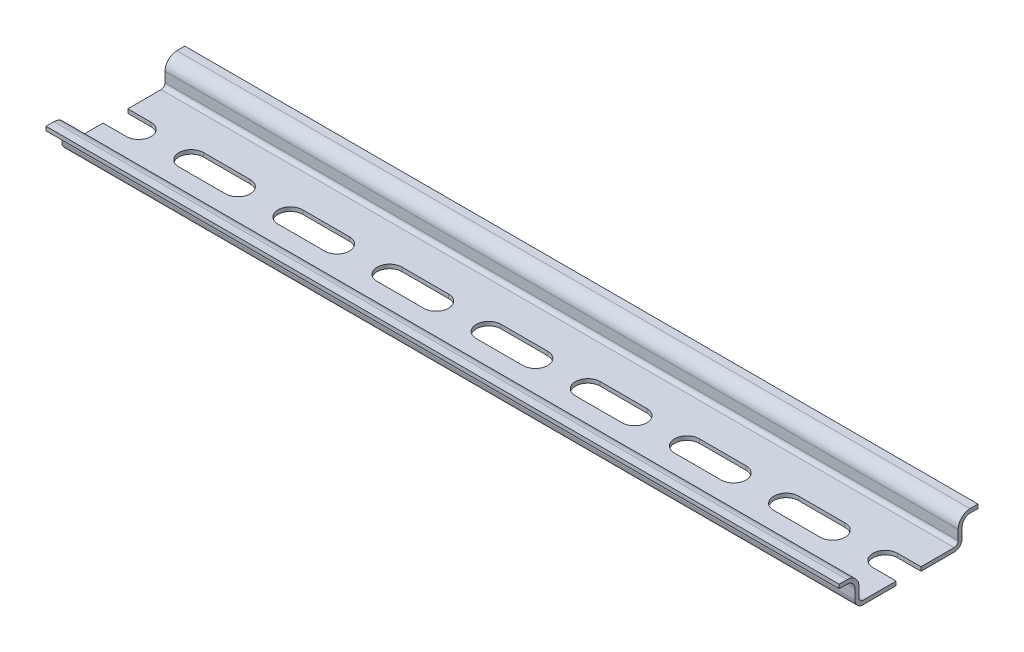
SolidWorks part; units mm, degrees
ref_plane "Front Plane" through (0, 0, 0) normal (0, 0, 1) x (1, 0, 0)
ref_plane "Top Plane" through (0, 0, 0) normal (0, 1, 0) x (1, 0, 0)
ref_plane "Right Plane" through (0, 0, 0) normal (1, 0, 0) x (0, 0, -1)
sketch "Sketch1" plane through (0, 0, 0) normal (1, 0, 0) x (0, 0, -1)
  line L0 (0, 0) -> (0, 18.2344) construction
  line L1 (0, 0) -> (26.621, 0) construction
  line L2 (-11.5, 0) -> (11.5, 0)
  line L3 (13.5, 2) -> (13.5, 4.5)
  line L4 (15.5, 6.5) -> (17.5, 6.5)
  line L5 (-13.5, 2) -> (-13.5, 4.5)
  line L6 (-15.5, 6.5) -> (-17.5, 6.5)
  arc A0 (13.5, 2) -> (11.5, 0) centre (11.5, 2) cw
  arc A1 (15.5, 6.5) -> (13.5, 4.5) centre (15.5, 4.5) ccw
  arc A2 (-13.5, 2) -> (-11.5, 0) centre (-11.5, 2) ccw
  arc A3 (-15.5, 6.5) -> (-13.5, 4.5) centre (-15.5, 4.5) cw
  point P9 (13.5, 0)
  dimension "D1" = 2
  dimension "D3" = 2
  dimension "D2" = 6.5
  dimension "D4" = 35
  dimension "D5" = 27
extrude "Extrude-Thin1" add sketch "Sketch1" along normal blind 200 thin thin type one direction wall 1
sketch "Sketch2" plane through (0, 0, 0) normal (0, -1, 0) x (1, 0, 0)
  line L0 (0, 6.6969) -> (0, 0) construction
  line L1 (0, 0) -> (9.9599, 0) construction
  line L2 (-5.875, 3.125) -> (5.875, 3.125)
  line L3 (-5.875, -3.125) -> (5.875, -3.125)
  arc A0 (5.875, 3.125) -> (5.875, -3.125) centre (5.875, 0) cw
  arc A1 (-5.875, 3.125) -> (-5.875, -3.125) centre (-5.875, 0) ccw
  point P6 (0, 3.125)
  point P12 (0, -3.125)
  dimension "D2" = 11.75
  dimension "D1" = 6.25
extrude "Cut-Extrude1" cut sketch "Sketch2" against normal up to next (1 mm away)
pattern_linear "LPattern1" count 9 spacing 25 along (1, 0, 0) of "Cut-Extrude1"
equation "\"length\"= 200mm"
equation "\"D1@Extrude-Thin1\"=\"length\""
equation "\"holes\"= \"length\" / 25 + 1"
equation "\"D1@LPattern1\"=\"holes\""
